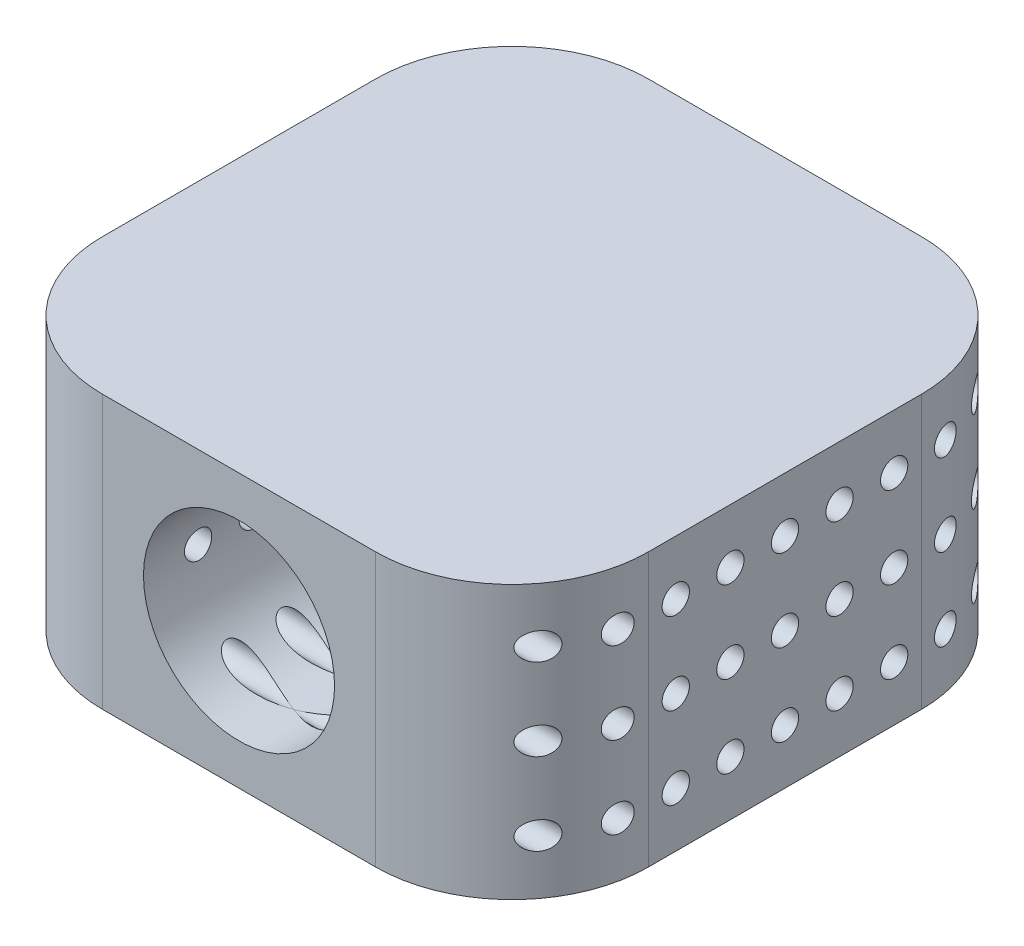
SolidWorks part; units mm, degrees
ref_plane "前视基准面" through (0, 0, 0) normal (0, 0, 1) x (1, 0, 0)
ref_plane "上视基准面" through (0, 0, 0) normal (0, 1, 0) x (1, 0, 0)
ref_plane "右视基准面" through (0, 0, 0) normal (1, 0, 0) x (0, 0, -1)
other "Configuration Table"
sketch "Sketch1" plane through (0, 0, 0) normal (0, 1, 0) x (1, 0, 0)
  line L1 (-5, -5) -> (5, -5)
  line L2 (-5, -5) -> (-5, 5)
  line L3 (-5, 5) -> (5, 5)
  line L4 (5, -5) -> (5, 5)
  line L5 (-5, -5) -> (5, 5) construction
  line L6 (-5, 5) -> (5, -5) construction
  point P0 (0, 0)
  dimension "D1" = 10
  dimension "D2" = 10
extrude "Boss-Extrude1" add sketch "Sketch1" along normal mid plane 5
sketch "Sketch3" plane through (-5, 0, 0) normal (-1, 0, 0) x (0, 0, 1)
  line L0 (0, 0) -> (1.5734, 0) construction
  line L1 (0, -1.1046) -> (0, 1.1046) construction
  circle A0 centre (0, 0) radius 0.25
  circle A1 centre (1, 0) radius 0.25
  circle A2 centre (2, 0) radius 0.25
  circle A3 centre (3, 0) radius 0.25
  circle A4 centre (4, 0) radius 0.25
  circle A5 centre (-4, 0) radius 0.25
  circle A6 centre (-3, 0) radius 0.25
  circle A7 centre (-2, 0) radius 0.25
  circle A8 centre (-1, 0) radius 0.25
  circle A9 centre (-4, 1.5) radius 0.25
  circle A10 centre (-3, 1.5) radius 0.25
  circle A11 centre (-2, 1.5) radius 0.25
  circle A12 centre (-1, 1.5) radius 0.25
  circle A13 centre (0, 1.5) radius 0.25
  circle A14 centre (1, 1.5) radius 0.25
  circle A15 centre (2, 1.5) radius 0.25
  circle A16 centre (3, 1.5) radius 0.25
  circle A17 centre (4, 1.5) radius 0.25
  circle A36 centre (4, -1.5) radius 0.25
  circle A37 centre (3, -1.5) radius 0.25
  circle A38 centre (2, -1.5) radius 0.25
  circle A39 centre (1, -1.5) radius 0.25
  circle A40 centre (0, -1.5) radius 0.25
  circle A41 centre (-1, -1.5) radius 0.25
  circle A42 centre (-2, -1.5) radius 0.25
  circle A43 centre (-3, -1.5) radius 0.25
  circle A44 centre (-4, -1.5) radius 0.25
  circle A45 centre (-4, 3) radius 0.25 [skipped]
  circle A46 centre (-3, 3) radius 0.25 [skipped]
  circle A47 centre (-2, 3) radius 0.25 [skipped]
  circle A48 centre (-1, 3) radius 0.25 [skipped]
  circle A49 centre (0, 3) radius 0.25 [skipped]
  circle A50 centre (1, 3) radius 0.25 [skipped]
  circle A51 centre (2, 3) radius 0.25 [skipped]
  circle A52 centre (3, 3) radius 0.25 [skipped]
  circle A53 centre (4, 3) radius 0.25 [skipped]
  dimension "D1" = 0.5
  dimension "D3" = 1.5
  dimension "D4" = 3
  dimension "D2" = 5
extrude "Cut-Extrude1" cut sketch "Sketch3" against normal through all
fillet "Fillet1" radius 2.5 4 edges at (5, 0, -5) (5, 0, 5) (-5, 0, -5) (-5, 0, 5)
sketch "Sketch4" plane through (0, 0, 5) normal (0, 0, 1) x (1, 0, 0)
  circle A0 centre (0, 0) radius 1.75
  dimension "D1" = 3.5
extrude "Cut-Extrude5" cut sketch "Sketch4" against normal through all
